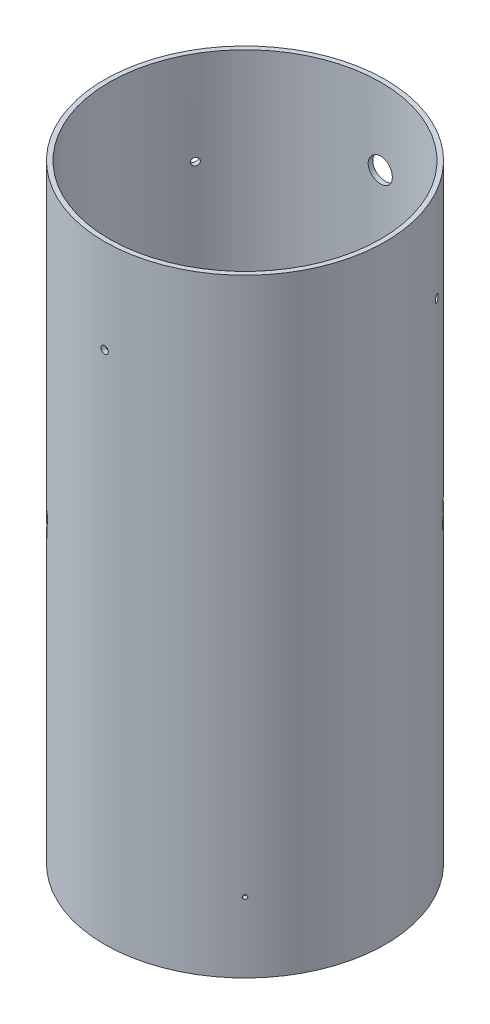
SolidWorks part; units mm, degrees
material "A-Glass Fiber"
ref_plane "Front Plane" through (0, 0, 0) normal (0, 0, 1) x (1, 0, 0)
ref_plane "Top Plane" through (0, 0, 0) normal (0, 1, 0) x (1, 0, 0)
ref_plane "Right Plane" through (0, 0, 0) normal (1, 0, 0) x (0, 0, -1)
sketch "Sketch1" plane through (0, 0, 0) normal (0, 1, 0) x (1, 0, 0)
  circle A0 centre (0, 0) radius 76.1746
  circle A1 centre (0, 0) radius 73.66
  dimension "D1" = 152.3492
  dimension "D2" = 147.32
extrude "Boss-Extrude1" add sketch "Sketch1" along normal blind 330.2
sketch "Sketch4" plane through (0, 0, 0) normal (0, 0, 1) x (1, 0, 0)
  line L0 (-76.1746, 0) -> (76.1746, 0) construction
  line L1 (76.1746, 330.2) -> (-76.1746, 330.2) construction
  line L2 (0, 330.2) -> (0, 0) construction
  line L3 (73.66, 330.2) -> (-73.66, 330.2) construction
  point P0 (0, 41.275)
  point P3 (0, 288.925)
  dimension "D1" = 41.275
  dimension "D2" = 41.275
hole_wizard "1/2 Clearance Hole5" positions "Sketch16" profile "Sketch17" hole size "1/2" standard "ANSI Inch"
sketch "Sketch16" plane through (0, 0, 0) normal (0, 0, 1) x (1, 0, 0)
  point P0 (0, 288.925)
sketch "Sketch17" plane through (0, 288.925, 0) normal (1, 0, 0) x (0, -1, 0)
  line L0 (0, 0) -> (0, 80.1345)
  line L1 (0, 80.1345) -> (6.5481, 76.2)
  line L2 (6.5481, 76.2) -> (6.5481, 0)
  line L5 (6.5481, 0) -> (0, 0)
  line L10 (0, 80.1345) -> (-6.5481, 76.2) construction
  line L11 (0, -6.35) -> (0, 107.95) construction
  dimension "Hole Dia." = 13.0962
  dimension "Hole Depth" = 76.2
  dimension "Drill Angle" = 118
hole_wizard "1/2 Clearance Hole7" positions "Sketch20" profile "Sketch21" hole size "1/2" standard "ANSI Inch"
sketch "Sketch20" plane through (0, 0, 0) normal (0, 0, 1) x (1, 0, 0)
  point P0 (0, 41.275)
sketch "Sketch21" plane through (0, 41.275, 0) normal (1, 0, 0) x (0, -1, 0)
  line L0 (0, 0) -> (0, 80.1345)
  line L1 (0, 80.1345) -> (6.5481, 76.2)
  line L2 (6.5481, 76.2) -> (6.5481, 0)
  line L5 (6.5481, 0) -> (0, 0)
  line L10 (0, 80.1345) -> (-6.5481, 76.2) construction
  line L11 (0, -6.35) -> (0, 107.95) construction
  dimension "Hole Dia." = 13.0962
  dimension "Hole Depth" = 76.2
  dimension "Drill Angle" = 118
ref_plane "Plane1" through (0, 0, 0) normal (-0.7071, 0, 0.7071) x (0.7071, 0, 0.7071)
sketch "Sketch23" plane through (0, 0, 0) normal (-0.7071, 0, 0.7071) x (0.7071, 0, 0.7071)
  line L0 (0, 0) -> (0, 330.2) construction
  line L1 (73.66, 330.2) -> (-73.66, 330.2) construction
  line L2 (-76.1746, 165.1) -> (76.1746, 165.1) construction
  line L3 (76.1746, 0) -> (76.1746, 330.2) construction
  circle A1 centre (0, 38.1) radius 1.0922
  point P12 (0, 165.1)
  dimension "D2" = 127
extrude "Shear Scrrews" cut sketch "Sketch23" against normal through all
pattern_circular "CirPattern1" count 4 over 360 about axis through (0, 330.2, 0) along (0, -1, 0) of "Shear Scrrews"
hole_wizard "Ø4.0 (4) Diameter Hole1" positions "Sketch24" profile "Sketch25" hole size "Ø4.0" standard "ANSI Metric"
sketch "Sketch24" plane through (0, 0, 0) normal (0, 0, 1) x (1, 0, 0)
  line L0 (76.1746, 330.2) -> (-76.1746, 330.2) construction
  point P0 (0, 279.4)
  dimension "D1" = 50.8
sketch "Sketch25" plane through (0, 279.4, 0) normal (1, 0, 0) x (0, 1, 0)
  line L0 (0, 0) -> (0, 90.1017)
  line L1 (0, 90.1017) -> (2, 88.9)
  line L2 (2, 88.9) -> (2, 0)
  line L5 (2, 0) -> (0, 0)
  line L10 (0, 90.1017) -> (-2, 88.9) construction
  line L11 (0, -6.35) -> (0, 107.95) construction
  dimension "Hole Dia." = 4
  dimension "Hole Depth" = 88.9
  dimension "Drill Angle" = 118
pattern_circular "CirPattern2" count 3 over 360 about axis through (0, 330.2, 0) along (0, 1, 0) of "Ø4.0 (4) Diameter Hole1"
ref_plane "Camera Cutout Plane" through (0, 0, 0) normal (0.7071, 0, -0.7071) x (0, -1, 0)
sketch "Sketch26" plane through (0, 0, 0) normal (0.7071, 0, -0.7071) x (0, -1, 0)
  line L0 (-330.2, 0) -> (0, 0) construction
  line L1 (-174.625, -5) -> (-167.625, -5)
  line L2 (-174.625, -5) -> (-174.625, 5)
  line L3 (-174.625, 5) -> (-167.625, 5)
  line L4 (-167.625, -5) -> (-167.625, 5)
  line L5 (-174.625, -5) -> (-167.625, 5) construction
  line L6 (-174.625, 5) -> (-167.625, -5) construction
  line L7 (-330.2, 76.1746) -> (-330.2, -76.1746) construction
  circle A0 centre (-158.735, 0) radius 2.75
  point P0 (-171.125, 0)
  dimension "D4" = 5.5
  dimension "D1" = 7
  dimension "D2" = 10
  dimension "D3" = 155.575
  dimension "D5" = 8.89
extrude "Upwards Camera Cutout" cut sketch "Sketch26" along normal through all
sketch "Sketch27" plane through (0, 0, 0) normal (0.7071, 0, -0.7071) x (0, -1, 0)
  line L0 (-330.2, 0) -> (0, 0) construction
  line L1 (-155.575, 5) -> (-162.575, 5)
  line L2 (-155.575, 5) -> (-155.575, -5)
  line L3 (-155.575, -5) -> (-162.575, -5)
  line L4 (-162.575, 5) -> (-162.575, -5)
  line L5 (-155.575, 5) -> (-162.575, -5) construction
  line L6 (-155.575, -5) -> (-162.575, 5) construction
  line L8 (0, -76.1746) -> (0, 76.1746) construction
  circle A0 centre (-171.465, 0) radius 2.75
  point P0 (-159.075, 0)
  dimension "D4" = 5.5
  dimension "D1" = 7
  dimension "D2" = 10
  dimension "D3" = 8.89
  dimension "D5" = 155.575
extrude "Downwards Camera Cutout" cut sketch "Sketch27" against normal through all
ref_plane "Camera Side Hole Plane" through (0, 0, 0) normal (0.7567, 0, -0.6537) x (0, -1, 0)
sketch "Sketch28" plane through (0, 0, 0) normal (0.7567, 0, -0.6537) x (0, -1, 0)
  line L0 (-330.2, 0) -> (0, 0) construction
  line L1 (-162.575, -10.5216) -> (-162.575, -0.5482) construction
  circle A0 centre (-166.385, 0) radius 2.75
  dimension "D1" = 5.5
  dimension "D2" = 3.81
extrude "Cut-Extrude4" cut sketch "Sketch28" against normal through all
pattern_circular "CirPattern3" count 2 every 8.407 about axis through (0, 0, 0) along (0, 1, 0) of "Cut-Extrude4"
sketch "Sketch29" plane through (0, 0, 0) normal (0.7567, 0, -0.6537) x (0, -1, 0)
  line L0 (-330.2, 0) -> (0, 0) construction
  line L1 (-167.625, 10.3381) -> (-167.625, 0.3647) construction
  circle A0 centre (-163.815, 0) radius 2.75
  dimension "D1" = 5.5
  dimension "D2" = 3.81
extrude "Cut-Extrude5" cut sketch "Sketch29" along normal through all
pattern_circular "CirPattern4" count 2 every 8.407 about axis through (0, 330.2, 0) along (0, 1, 0) of "Cut-Extrude5"
equation "\"Mid_Coupler_Length\" = 13in"
equation "\"D1@Boss-Extrude1\"=\"Mid_Coupler_Length\""
equation "\"Shear_Screw_Coupler_Location\" = 4.5in"
equation "\"Shear_Screw_Diameter\" = 0.086in"
equation "\"D2@Sketch23\"=\"Shear_Screw_Coupler_Location\"+0.5"
equation "\"Mid_Tube_Length\"= 1in"
equation "\"Bodytube_OD\" = 6.17in"
equation "\"Bodytube_ID\" = 5.998in"
equation "\"Camera_Cutout_Width\"=10mm"
equation "\"Camera_Cutout_Height\"=7mm"
equation "\"Fwd_Tube_Length\" = 40in"
equation "\"BKHD_Screw_Diam\"= 3.5mm"
equation "\"Fwd_BKHD_From_Top\" = 18in"
equation "\"Motor_OD\" = 4in"
equation "\"Aft_Section_Length\"= 39in"
equation "\"AB_Coupler_OD_Length\"= 1in"
equation "\"AB_Coupling_Section_Length\"= 0.375in"
equation "\"AB_Coupler_Length\"= \"AB_Coupler_OD_Length\" + \"AB_Coupling_Section_Length\" * 2"
equation "\"Cutout_Angle\" = 80"
equation "\"AB_Paddle_Height\" = 0.375in"
equation "\"AB_Coupler_Num_Screws\"= 4"
equation "\"AB_BKHD_Thickness\" = 0.375in"
equation "\"AB_Mount_From_Bottom\" = 23.175in"
equation "\"Num_Cutouts\" = 3"
equation "\"AB_Coupler_OD\"= 6.17in"
equation "\"AB_Coupler_ID\"= 5.75in"
equation "\"AB_Coupler_Surface_Diameter\"= 5.998in"
equation "\"AB_Coupling_Screw_Diameter\"= 0.15748in"
equation "\"AB_Central_Bushing_Length\" = .4724in"
equation "\"Lead_Screw_Dist\" = 3.4in"
equation "\"Lead_Screw_Diam\" = 0.386in"
equation "\"Lead_Screw_Length\" = (\"Mid_Coupler_Length\" + 2*0.375in + 2*0.5in)"
equation "\"Paddle_Pin_Offset\" = .25in"
equation "\"Paddle_Pin_Radius\" = 2.25in"
equation "\"SS_Paddle_Pin_Radius\" = 2.25*0.66in"
equation "\"Paddle_Gear_OD\" = 3.2in"
equation "\"Drive_Gear_OD\" = 1.7in"
equation "\"Fin_Thickness\"= .118in"
equation "\"Guiderail_Cutout_Diameter\"= 1.5in"
equation "\"DB9_Hole_Dist\" = 25mm"
equation "\"DB9_Relief_Width\" = 0.47in"
equation "\"DB9_Relief_Hole_Offset\" = 0.09in"
equation "\"Airbrakes_Wire_Hole_Dia\" = .25in"
equation "\"Airbrakes_Wire_Hole_Dist\" = 1.1in"
equation "\"Servo_Gear_Offset\" = 0.5in"
equation "\"FWD_Shear_Screw_Dist\" = 1.5in"
equation "\"Camera_Screw_Dia\" = 0.216535"
equation "\"Camera_Hole_Angle\" = atn ( 2 / 3 * tan ( 12.5deg ) )"
equation "\"D1@Sketch26\"=\"Camera_Cutout_Height\""
equation "\"D2@Sketch26\"=\"Camera_Cutout_Width\""
equation "\"D3@Sketch26\"=6.125"
equation "\"D1@Sketch27\"=\"Camera_Cutout_Height\""
equation "\"D2@Sketch27\"=\"Camera_Cutout_Width\""
equation "\"D1@Sketch28\"=\"Camera_Screw_Dia\""
equation "\"D2@CirPattern3\"=\"Camera_Hole_Angle\""
equation "\"D1@Sketch29\"=\"Camera_Screw_Dia\""
equation "\"D2@CirPattern4\"=\"Camera_Hole_Angle\""
equation "\"Coupler_OD\" = 5.998"
equation "\"D1@Sketch1\"=\"Coupler_OD\""
equation "\"Coupler_ID\" = 5.8"
equation "\"D2@Sketch1\"=\"Coupler_ID\""
